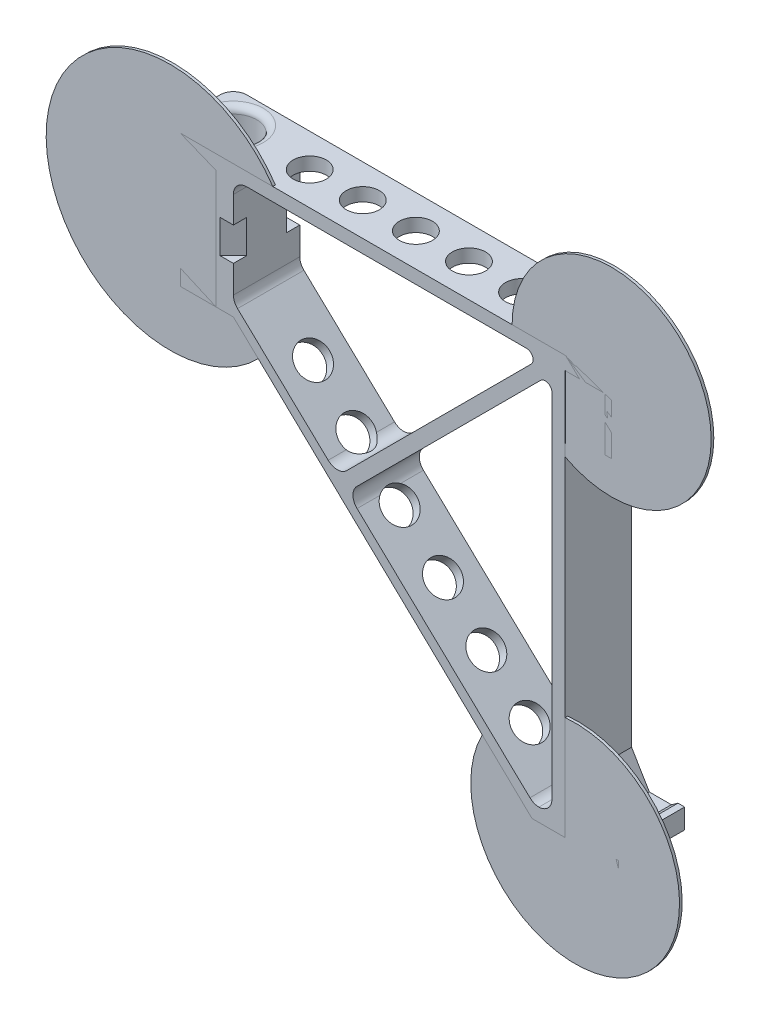
SolidWorks part; units mm, degrees
ref_plane "Front Plane" through (0, 0, 0) normal (0, 0, 1) x (1, 0, 0)
ref_plane "Top Plane" through (0, 0, 0) normal (0, 1, 0) x (1, 0, 0)
ref_plane "Right Plane" through (0, 0, 0) normal (1, 0, 0) x (0, 0, -1)
sketch "Sketch1" plane through (0, 0, 0) normal (0, 0, 1) x (1, 0, 0)
  line L0 (-8, 44.65) -> (-8, 60.65)
  line L1 (-8, 62.65) -> (49, 62.65)
  line L2 (49, 62.65) -> (49, 52.65)
  line L3 (49, 52.65) -> (48, 52.65)
  line L4 (48, 52.65) -> (48, 60.65)
  line L5 (48, 60.65) -> (42, 60.65)
  line L6 (42, 60.65) -> (42, 6.5)
  line L7 (37, -0.2965) -> (50, -0.2965)
  line L8 (-8, 42.65) -> (37, -0.2965)
  line L9 (50, -0.2965) -> (50, 2.7035)
  line L10 (50, 2.7035) -> (49, 2.7035)
  line L11 (49, 2.7035) -> (48, 2)
  line L12 (48, 2) -> (44.7, 2)
  line L13 (44.7, 2) -> (42, 6.5)
  line L14 (-8, 42.65) -> (-18, 42.65)
  line L15 (-18, 42.65) -> (-18, 62.65)
  line L16 (-18, 62.65) -> (-8, 62.65)
  line L17 (-8, 60.65) -> (38.5858, 60.65)
  line L18 (40, 59.2358) -> (40, 1.7035)
  line L19 (40, 1.7035) -> (37.268, 1.7035)
  line L20 (37.268, 1.7035) -> (9.1468, 28.3826)
  line L21 (40, 60.65) -> (8.4211, 29.0711) construction
  line L22 (38.5858, 60.65) -> (7.6954, 29.7596)
  line L23 (9.1468, 28.3826) -> (40, 59.2358)
  line L24 (7.6954, 29.7596) -> (-8, 44.65)
  dimension "D1" = 1
  dimension "D2" = 10
  dimension "D3" = 2
  dimension "D4" = 5
  dimension "D5" = 8
  dimension "D6" = 6
  dimension "D7" = 54.15
  dimension "D8" = 4.5
  dimension "D9" = 2.7
  dimension "D10" = 3.3
  dimension "D11" = 3
  dimension "D12" = 1
  dimension "D13" = 50
  dimension "D14" = 58.65
  dimension "D15" = 20
  dimension "D16" = 10
  dimension "D17" = 2
  dimension "D18" = 2
  dimension "D19" = 2
  dimension "D20" = 1
  dimension "D21" = 2
extrude "Frame" add sketch "Sketch1" along normal blind 10
sketch "Sketch13" plane through (0, 42.65, 0) normal (0, -1, 0) x (1, 0, 0)
  line L0 (-18, 0) -> (-8, 0) construction
  line L1 (-18, 10) -> (-18, 0) construction
  circle A0 centre (-13, 5) radius 3.5
  point P2 (-13, 0)
  dimension "D1" = 7
  dimension "D2" = 5
  dimension "D3" = 5
extrude "Cut-Extrude7" cut sketch "Sketch13" against normal through all
fillet "Fillet4" radius 1 2 edges at (-13, 62.65, 1.5) (-13, 42.65, 1.5)
sketch "Sketch14" plane through (0, 0, 10) normal (0, 0, 1) x (1, 0, 0)
  line L0 (-18, 62.65) -> (-18, 42.65) construction
  line L1 (-18, 54.65) -> (-13, 54.65)
  line L2 (-18, 54.65) -> (-18, 49.65)
  line L3 (-18, 49.65) -> (-13, 49.65)
  line L4 (-13, 54.65) -> (-13, 49.65)
  line L5 (-18, 42.65) -> (-8, 42.65) construction
  dimension "D1" = 5
  dimension "D2" = 7
  dimension "D3" = 5
extrude "Cut-Extrude8" cut sketch "Sketch14" against normal through all
fillet "Fillet5" radius 2 4 edges at (-18, 46.15, 0) (-18, 58.65, 0) (-18, 46.15, 10) (-18, 58.65, 10)
ref_plane "Plane1" through (0, 49.65, 0) normal (0, 1, 0) x (1, 0, 0)
sketch "Sketch15" plane through (0, 49.65, 0) normal (0, 1, 0) x (1, 0, 0)
  line L0 (-10, 0) -> (-8, -2)
  line L1 (49, 0) -> (-16, 0) construction
  line L2 (-8, -10) -> (-8, 0) construction
  line L3 (-8, -2) -> (-8, 0)
  line L4 (-8, 0) -> (-10, 0)
  line L5 (-10, -10) -> (-8, -8)
  line L6 (49, -10) -> (-16, -10) construction
  line L7 (-8, -8) -> (-8, -10)
  line L8 (-8, -10) -> (-10, -10)
  dimension "D1" = 2
  dimension "D2" = 2
  dimension "D3" = 2
  dimension "D4" = 2
extrude "Cut-Extrude9" cut sketch "Sketch15" along normal blind 5
chamfer "Chamfer1" distance 1 angle 45 2 edges at (-13, 52.15, 10) (-13, 52.15, 0)
fillet "Fillet6" radius 2 6 edges at (-8, 60.65, 5) (40, 1.7035, 5) (37.268, 1.7035, 5) (-8, 44.65, 5) (9.1468, 28.3826, 5) (7.6954, 29.7596, 5)
fillet "Fillet7" radius 1 2 edges at (40, 59.2358, 5) (38.5858, 60.65, 5)
sketch "Sketch18" plane through (17.4885, 18.3247, 0) normal (-0.6904, -0.7234, 0) x (0.7234, -0.6904, 0)
  line L0 (-35.2333, 10) -> (26.9712, 10) construction
  circle A0 centre (-26.969, 5) radius 2.5
  circle A1 centre (-17.969, 5) radius 2.5
  circle A2 centre (-8.969, 5) radius 2.5
  circle A3 centre (0.031, 5) radius 2.5
  circle A4 centre (9.031, 5) radius 2.5
  circle A5 centre (18.031, 5) radius 2.5
  dimension "D2" = 5
  dimension "D1" = 5
  dimension "D3" = 6
extrude "Cut-Extrude11" cut sketch "Sketch18" against normal up to next
sketch "Sketch19" plane through (0, 62.65, 0) normal (0, 1, 0) x (1, 0, 0)
  line L0 (49, 0) -> (-16, 0) construction
  circle A0 centre (-1.5, -5) radius 2.5
  arc A1 (-13, -1.5) -> (-13, -8.5) centre (-13, -5) ccw construction
  circle A2 centre (6.5, -5) radius 2.5
  circle A3 centre (14.5, -5) radius 2.5
  circle A4 centre (22.5, -5) radius 2.5
  circle A5 centre (30.5, -5) radius 2.5
  point P6 (-16.5, -5)
  dimension "D2" = 5
  dimension "D1" = 5
  dimension "D3" = 15
  dimension "D4" = 5
extrude "Cut-Extrude12" cut sketch "Sketch19" against normal up to next
sketch "Sketch17" plane through (0, 0, 10) normal (0, 0, 1) x (1, 0, 0)
  line L0 (49, 62.65) -> (-16, 62.65) construction
  line L1 (34, 62.65) -> (42.0673, 62.65)
  line L2 (42.0673, 62.65) -> (42, 49.3835)
  line L3 (42, 6.5) -> (42, 60.65) construction
  line L4 (37, -0.2965) -> (50, -0.2965) construction
  line L5 (29.4949, 6.8661) -> (37, -0.2965)
  line L6 (-8, 42.65) -> (37, -0.2965) construction
  line L7 (37, -0.2965) -> (42, -0.2965)
  line L8 (42, -0.2965) -> (42, 15.3622)
  line L9 (-2.0671, 62.65) -> (-10.5875, 62.65)
  line L11 (-8, 42.65) -> (-4.2532, 39.0742)
  line L12 (-10.5875, 62.65) -> (-10.5875, 42.65)
  line L13 (-16, 42.65) -> (-8, 42.65) construction
  line L14 (-10.5875, 42.65) -> (-8, 42.65)
  arc A0 (-2.0671, 62.65) -> (-4.2532, 39.0742) centre (-17.5426, 52.1957) ccw
  arc A1 (42, 49.3835) -> (34, 62.65) centre (49, 62.65) ccw
  arc A2 (29.4949, 6.8661) -> (42, 15.3622) centre (43.5, -0.2965) ccw
  dimension "D3" = 30
extrude "ears" add sketch "Sketch17" against normal blind 0.4 separate body
